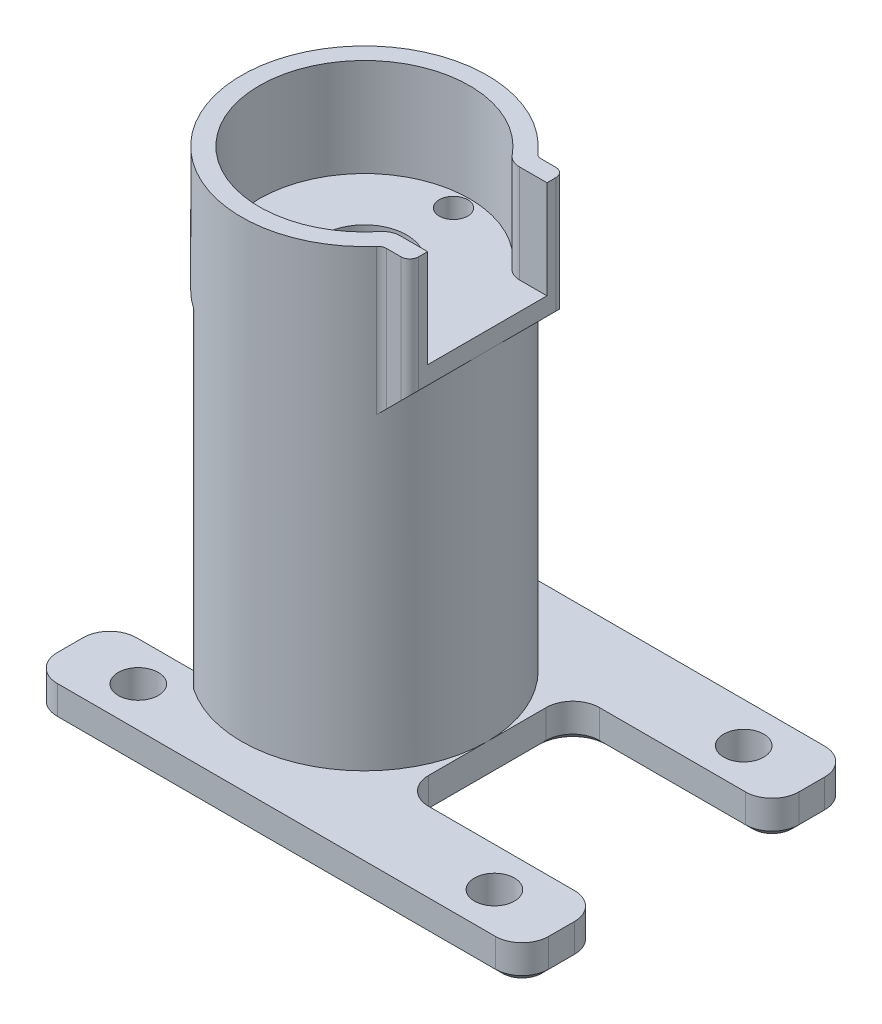
SolidWorks part; units mm, degrees
ref_plane "Front Plane" through (0, 0, 0) normal (0, 0, 1) x (1, 0, 0)
ref_plane "Top Plane" through (0, 0, 0) normal (0, 1, 0) x (1, 0, 0)
ref_plane "Right Plane" through (0, 0, 0) normal (1, 0, 0) x (0, 0, -1)
sketch "Sketch1" plane through (0, 0, 0) normal (0, 1, 0) x (1, 0, 0)
  line L1 (-20, -14) -> (20, -14) construction
  line L2 (-20, -14) -> (-20, 14) construction
  line L3 (-20, 14) -> (20, 14) construction
  line L4 (20, -14) -> (20, 14) construction
  line L5 (-20, -14) -> (20, 14) construction
  line L6 (-20, 14) -> (20, -14) construction
  line L7 (-29.1, -20) -> (29.1, -20)
  line L8 (-29.1, -20) -> (-29.1, 20)
  line L9 (-29.1, 20) -> (29.1, 20)
  line L10 (29.1, -20) -> (29.1, 20)
  line L11 (-29.1, -20) -> (29.1, 20) construction
  line L12 (-29.1, 20) -> (29.1, -20) construction
  circle A0 centre (-20, 14) radius 2
  circle A1 centre (20, 14) radius 2
  circle A2 centre (20, -14) radius 2
  circle A3 centre (-20, -14) radius 2
  circle A4 centre (-8.6, 0) radius 9.1
  circle A5 centre (-8.6, 0) radius 4
  circle A6 centre (-20, -14) radius 3.75 construction
  point P0 (0, 0)
  point P10 (0, 0)
  point P18 (-29.1, 0)
  dimension "D3" = 4
  dimension "D7" = 18.2
  dimension "D8" = 8
  dimension "D9" = 7.5
  dimension "D1" = 40
  dimension "D2" = 28
  dimension "D4" = 40
  dimension "D5" = 58.2
  dimension "D6" = 20.5
sketch "Sketch2" plane through (0, 0, 0) normal (0, 1, 0) x (1, 0, 0)
  line L8 (-28.6, -19.5) -> (28.6, -19.5)
  line L9 (28.6, -19.5) -> (28.6, 19.5)
  line L10 (28.6, 19.5) -> (-28.6, 19.5)
  line L11 (-28.6, 19.5) -> (-28.6, -19.5)
  line L12 (-28.6, -19.5) -> (28.6, -19.5)
  line L13 (28.6, -19.5) -> (28.6, 19.5)
  line L14 (28.6, 19.5) -> (-28.6, 19.5)
  line L15 (-28.6, 19.5) -> (-28.6, -19.5)
  circle A22 centre (-20, 14) radius 2 construction
  circle A24 centre (20, 14) radius 2 construction
  circle A26 centre (20, -14) radius 2 construction
  circle A29 centre (-20, -14) radius 2 construction
  circle A30 centre (-20, -14) radius 2
  circle A31 centre (20, -14) radius 2
  circle A32 centre (20, 14) radius 2
  circle A33 centre (-20, 14) radius 2
  circle A34 centre (-20, 14) radius 2.25
  circle A35 centre (20, 14) radius 2.25
  circle A36 centre (20, -14) radius 2.25
  circle A37 centre (-20, -14) radius 2.25
  circle A40 centre (-8.6, 0) radius 9.35
  circle A41 centre (-8.6, 0) radius 9.35
  dimension "D1" = 0.5
  dimension "D2" = 0.25
  dimension "D3" = 0.25
ref_plane "Plane1" through (0, 55, 0) normal (0, 1, 0) x (1, 0, 0)
sketch "Sketch4" plane through (0, 55, 0) normal (0, 1, 0) x (1, 0, 0)
  line L1 (0.8868, -6.5) -> (3.9, -6.5)
  line L2 (0.8868, -6.5) -> (0.8868, 6.5) construction
  line L3 (0.8868, 6.5) -> (3.9, 6.5)
  line L4 (3.9, -6.5) -> (3.9, 6.5)
  circle A0 centre (-8.6, 0) radius 9.1 construction
  circle A1 centre (-8.6, 0) radius 9.1 construction
  circle A2 centre (-8.6, 0) radius 11.5
  circle A3 centre (-8.6, 10) radius 1.4
  dimension "D1" = 23
  dimension "D4" = 2.8
  dimension "D2" = 12.5
  dimension "D3" = 13
  dimension "D5" = 10
sketch "Sketch5" plane through (0, 55, 0) normal (0, 1, 0) x (1, 0, 0)
  line L0 (4.1, -6.7) -> (5.2, -6.7)
  line L1 (4.1, 6.7) -> (5.2, 6.7)
  line L2 (4.1, -6.7) -> (4.1, -13.8)
  line L3 (-22.4, -13.8) -> (5.2, -13.8)
  line L4 (-22.4, -13.8) -> (-22.4, 13.8)
  line L5 (2.1121, -8.7) -> (5.2, -8.7)
  line L7 (5.2, 8.7) -> (2.1121, 8.7)
  line L8 (4.1, 6.7) -> (0.8868, 6.7)
  line L9 (4.1, -6.7) -> (4.1, 6.7)
  line L10 (0.8868, -6.7) -> (4.1, -6.7)
  line L11 (4.1, 6.7) -> (1.1134, 6.7)
  line L12 (4.1, -6.7) -> (4.1, 6.7)
  line L13 (1.1134, -6.7) -> (4.1, -6.7)
  line L14 (-22.4, 13.8) -> (5.2, 13.8)
  line L15 (1.1134, -8.7) -> (6.1, -8.7) construction
  line L16 (6.1, 8.7) -> (1.1134, 8.7) construction
  line L17 (5.2, -13.8) -> (5.2, 13.8)
  line L18 (-22.4, -13.8) -> (5.2, 13.8) construction
  line L19 (-22.4, 13.8) -> (5.2, -13.8) construction
  line L20 (6.1, -8.7) -> (6.1, 8.7) construction
  line L21 (4.1, 6.7) -> (4.1, 13.8)
  arc A0 (2.1121, 8.7) -> (2.0363, 8.7925) centre (-8.6, 0) cw
  circle A2 centre (-8.6, 0) radius 11.8
  arc A3 (1.1134, 6.7) -> (1.1134, -6.7) centre (-8.6, 0) ccw
  arc A4 (2.1121, 8.7) -> (2.1121, -8.7) centre (-8.6, 0) ccw
  circle A7 centre (-8.6, 0) radius 13.8 construction
  circle A8 centre (-8.6, 0) radius 11.8 construction
  point P3 (2.5888, 3.4207)
  point P14 (5.4577, 4.2979)
  dimension "D1" = 0.3
  dimension "D2" = 0.2
  dimension "D3" = 2
sketch "Sketch7" plane through (0, 0, 0) normal (0, 1, 0) x (1, 0, 0)
  line L0 (27.6, -18.5) -> (78.6, -18.5)
  line L1 (27.6, 18.5) -> (78.6, 18.5)
  line L4 (-8.6, -9.6) -> (-27.6, -9.6) construction
  line L5 (-8.6, 9.6) -> (-27.6, 9.6) construction
  line L8 (27.6, 18.5) -> (-27.6, 18.5)
  line L9 (27.6, -18.5) -> (27.6, 18.5)
  line L10 (-27.6, -18.5) -> (27.6, -18.5)
  line L11 (-27.6, 18.5) -> (-27.6, -18.5)
  line L12 (27.6, 18.5) -> (-27.6, 18.5)
  line L13 (27.6, -18.5) -> (27.6, 18.5)
  line L14 (-27.6, -18.5) -> (27.6, -18.5)
  line L15 (-27.6, 18.5) -> (-27.6, -18.5)
  line L17 (78.6, 18.5) -> (78.6, -18.5)
  line L19 (28.6, -19.5) -> (28.6, 19.5) construction
  line L20 (5.2, 0) -> (5.2, -18.5) construction
  line L21 (5.2, 0) -> (5.2, 18.5) construction
  line L22 (5.2, -9.6) -> (27.6, -9.6) construction
  line L23 (5.2, 9.6) -> (27.6, 9.6) construction
  arc A0 (2.0363, 8.7925) -> (2.1121, 8.7) centre (-8.6, 0) ccw construction
  circle A1 centre (-8.6, 0) radius 13.8 construction
  circle A11 centre (-8.6, 0) radius 9.6
  circle A12 centre (-8.6, 0) radius 9.6 construction
  dimension "D2" = 0.25
  dimension "D4" = 50
  dimension "D1" = 1
extrude "Boss-Extrude10" add sketch "Sketch5" against normal up to vertex (55 mm away) contours A0 A4 L13 A3 L11 | L11 A3 L13 A0 L12 | A0 L12 region at (3.6759, 55, 5.9976) region at (4.5415, 55, 0) region at (2.5188, 55, 7.5178) region at (-8.6, 55, 0) up to point (-8.6, 0, 0)
extrude "Boss-Extrude13" add sketch "Sketch5<9>" against normal blind 13 contours L13 A0 L5 L2 | L5 L17 L0 L2 | L12 A0 L13 | L17 A0 L12 L0 | L12 A0 L17 L1 | L11 A0 L12 | L7 A0 L11 L21 | L21 L1 L17 L7 region at (4.7782, 55, 4.903) region at (4.65, 55, 7.7) region at (3.8927, 55, 6.2763) region at (3.4055, 55, 7.8772) region at (4.7782, 55, -4.903) region at (3.8927, 55, -6.2763) region at (4.65, 55, -7.7) region at (3.4055, 55, -7.8772)
sketch "Sketch5<9>" plane through (0, 55, 0) normal (0, 1, 0) x (1, 0, 0) same geometry as "Sketch5"
extrude "Boss-Extrude11" add sketch "Sketch7" along normal blind 4 contours L12 L15 L14 L13 region at (1.4205, 0, 0)
ref_plane "Plane2" through (0, 44, 0) normal (0, 1, 0) x (1, 0, 0)
ref_plane "Plane5" through (0, 41, 0) normal (0, 1, 0) x (1, 0, 0)
sketch "Sketch14" plane through (0, 41, 0) normal (0, 1, 0) x (1, 0, 0)
  line L0 (-8.6, -9.6) -> (-27.6, -9.6) construction
  line L1 (-8.6, 9.6) -> (-27.6, 9.6) construction
  line L2 (-8.6, -9.6) -> (-28.6, -9.6)
  line L3 (-8.6, 9.6) -> (-28.6, 9.6)
  line L4 (-28.6, 9.6) -> (-28.6, -9.6)
  line L5 (-28.6, 19.5) -> (-28.6, -19.5) construction
  line L6 (27.6, -18.5) -> (27.6, 18.5) construction
  line L10 (27.6, -18.5) -> (27.6, 18.5)
  line L15 (5.2, 9.6) -> (27.6, 9.6) construction
  line L16 (5.2, -9.6) -> (27.6, -9.6) construction
  line L17 (5.2, 9.6) -> (27.6, 9.6)
  line L18 (5.2, -9.6) -> (27.6, -9.6)
  line L19 (5.2, 0) -> (5.2, 18.5) construction
  line L20 (5.2, 0) -> (5.2, -18.5) construction
  line L21 (5.2, 0) -> (5.2, 18.5)
  line L22 (5.2, 0) -> (5.2, -18.5)
  circle A0 centre (-8.6, 0) radius 9.6 construction
  circle A1 centre (-8.6, 0) radius 9.6
extrude "Cut-Extrude9" cut sketch "Sketch14" against normal through all contours L3 L4 L2 | L3 L2 A1 | A1 | L10 region at (-22.1857, 41, 0) region at (-8.6, 41, 0) region at (16.4, 41, 0)
fillet "Fillet1" radius 1 2 edges at (-18.5136, 22.5, -9.6) (-18.5136, 22.5, 9.6)
fillet "Fillet3" radius 3 10 edges at (-27.6, 2, 9.6) (-27.6, 2, -9.6) (-27.6, 2, -18.5) (27.6, 2, -18.5) (27.6, 2, 18.5) (-27.6, 2, 18.5) (27.6, 2, -9.6) (5.2, 2, -9.6) (5.2, 2, 9.6) (27.6, 2, 9.6)
extrude "Cut-Extrude11" cut sketch "Sketch2" against normal through all and the other way through all contours A34 | A37 | A36 | A35
sketch "Sketch15" plane through (0, 55, 0) normal (0, 1, 0) x (1, 0, 0)
  line L0 (5.2, -13.8) -> (5.2, 13.8) construction
  line L1 (4.1, 6.7) -> (5.2, 6.7) construction
  line L2 (4.1, 6.7) -> (1.1134, 6.7) construction
  line L3 (1.1134, -6.7) -> (4.1, -6.7) construction
  line L4 (4.1, -6.7) -> (5.2, -6.7) construction
  line L5 (5.2, -13.8) -> (5.2, 13.8)
  line L6 (4.1, 6.7) -> (5.2, 6.7)
  line L7 (4.1, 6.7) -> (1.1134, 6.7)
  line L8 (1.1134, -6.7) -> (4.1, -6.7)
  line L9 (4.1, -6.7) -> (5.2, -6.7)
  arc A0 (1.1134, 6.7) -> (1.1134, -6.7) centre (-8.6, 0) ccw construction
  arc A1 (1.1134, 6.7) -> (1.1134, -6.7) centre (-8.6, 0) ccw
extrude "Cut-Extrude12" cut sketch "Sketch15" against normal blind 11 contours L7 A1 L8 L9 L5 L6 region at (-7.6632, 55, 0)
chamfer "Chamfer1" distance 0.8 angle 45 21 edges at (-27.6, 0, 14.05) (-26.7213, 0, 10.4787) (-26.7213, 0, 17.6213) (-16.6, 0, 9.6) (0, 0, 18.5) (1, 0, 0) (26.7213, 0, 17.6213) (-16.6, 0, -9.6) (-26.7213, 0, -10.4787) (26.7213, 0, -17.6213) (-27.6, 0, -14.05) (0, 0, -18.5) (-26.7213, 0, -17.6213) (27.6, 0, -14.05) (26.7213, 0, 10.4787) (16.4, 0, 9.6) (6.0787, 0, 8.7213) (5.2, 0, 0) (6.0787, 0, -8.7213) (16.4, 0, -9.6) (26.7213, 0, -10.4787)
fillet "Fillet7" radius 1 4 edges at (2.1121, 48.5, -8.7) (2.1121, 48.5, 8.7) (5.2, 48.5, -8.7) (5.2, 48.5, 8.7)
sketch "Sketch16" plane through (0, 44, 0) normal (0, 1, 0) x (1, 0, 0)
  circle A0 centre (-8.6, 0) radius 4.75
  dimension "D1" = 9.5
extrude "Cut-Extrude13" cut sketch "Sketch16" against normal through all
sketch "Sketch17" plane through (0, 44, 0) normal (0, 1, 0) x (1, 0, 0)
  line L0 (-8.6, 0) -> (-8.6, 10) construction
  circle A0 centre (-8.6, 10) radius 1.6
  dimension "D2" = 3.2
  dimension "D1" = 10
extrude "Cut-Extrude14" cut sketch "Sketch17" against normal blind 3
fillet "Fillet8" radius 2 2 edges at (1.1134, 49.5, 6.7) (1.1134, 49.5, -6.7)
draft "Draft1" type of draft neutral plane draft angle 45 faces to draft 2 face at (3.9975, 42, -6.9149) face at (3.9975, 42, 6.9149) neutral plane through (5.2, 42, 0) neutral plane normal (1, 0, 0) parameters "D1"=45
